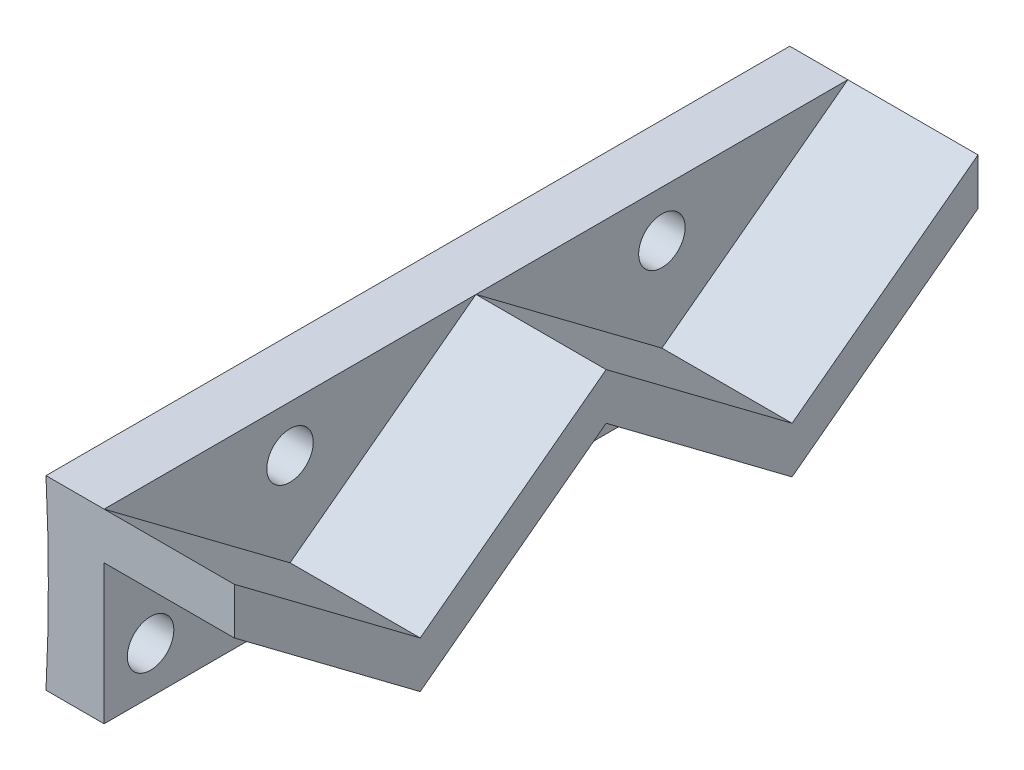
SolidWorks part; units mm, degrees
material "Polyetheretherketone (PEEK)"
ref_plane "Front Plane" through (0, 0, 0) normal (0, 0, 1) x (1, 0, 0)
ref_plane "Top Plane" through (0, 0, 0) normal (0, 1, 0) x (1, 0, 0)
ref_plane "Right Plane" through (0, 0, 0) normal (1, 0, 0) x (0, 0, -1)
sketch "Sketch1" plane through (0, 0, 0) normal (0, 0, 1) x (1, 0, 0)
  circle A0 centre (0, 0) radius 127
  dimension "D1" = 254
extrude "Boss-Extrude1" add sketch "Sketch1" along normal blind 50.8
ref_plane "Plane1" through (139.7, 0, 0) normal (1, 0, 0) x (0, 0, -1)
sketch "Sketch2" plane through (139.7, 0, 0) normal (1, 0, 0) x (0, 0, -1)
  line L0 (0, 0) -> (-25.4, 0)
  line L1 (0, 6.35) -> (-25.4, 6.35)
  line L2 (0, -6.35) -> (-25.4, -6.35)
  line L3 (-25.4, 0) -> (-25.4, -6.35)
  line L4 (0, 6.35) -> (0, -6.35)
  line L5 (-25.4, 6.35) -> (-12.7, -3.175)
  line L6 (-12.7, -3.175) -> (0, 6.35)
  line L7 (-25.4, 3.175) -> (-12.7, -6.35)
  line L8 (-12.7, -6.35) -> (0, 3.175)
  line L9 (-25.4, 6.35) -> (-25.4, 0)
  circle A0 centre (-22.225, -3.175) radius 1.5875
  circle A1 centre (-12.7, 3.175) radius 1.5875
  circle A2 centre (-3.175, -3.175) radius 1.5875
  dimension "D6" = 3.175
  dimension "D1" = 25.4
  dimension "D4" = 3.175
  dimension "D5" = 3.175
  dimension "D7" = 3.175
  dimension "D8" = 3.175
  dimension "D9" = 3.175
  dimension "D2" = 6.35
  dimension "D3" = 6.35
extrude "Boss-Extrude2" add sketch "Sketch2" against normal blind 15.24 separate body contours L8 L2 L4 L0 A2 | L8 L0 L4 | L0 L6 L1 L5 A1 | L5 L6 L0 | L7 L0 L3 L2 A0 | L7 L9 L0 | L7 L8 L0 L6 L5 | L5 L9 L7 L0 | L0 L8 L4 L6 region at (139.7, -3.7956, 4.8298) region at (139.7, 1.0583, 1.4111) region at (139.7, -3.0303, 8.5752) region at (139.7, 2.4694, 3.2926) region at (139.7, -1.0583, 12.7) region at (139.7, 0.2618, 12.7) region at (139.7, -3.7956, 20.5702) region at (139.7, 2.4694, 22.1074) region at (139.7, 1.0583, 23.9889)
extrude "Cut-Extrude1" cut sketch "Sketch2<4>" against normal blind 8.89 contours L8 L2 L4 L0 A2 | L8 L0 L4 | L0 L6 L1 L5 A1 | L7 L9 L0 | L5 L6 L0 | L7 L0 L3 L2 A0 region at (139.7, -3.7956, 4.8298) region at (139.7, 1.0583, 1.4111) region at (139.7, -1.0583, 12.7) region at (139.7, 0.2618, 12.7) region at (139.7, -3.7956, 20.5702) region at (139.7, 1.0583, 23.9889)
sketch "Sketch2<4>" plane through (139.7, 0, 0) normal (1, 0, 0) x (0, 0, -1) same geometry as "Sketch2"
pattern_linear "LPattern1" count 2 spacing 25.4 along (0, 0, 1) of bodies 105
combine bodies "Combine1" operation type add bodies to combine 106 105
extrude "Cut-Extrude2" cut sketch "Sketch1<2>" along normal through all
sketch "Sketch1<2>" plane through (0, 0, 0) normal (0, 0, 1) x (1, 0, 0) same geometry as "Sketch1"
